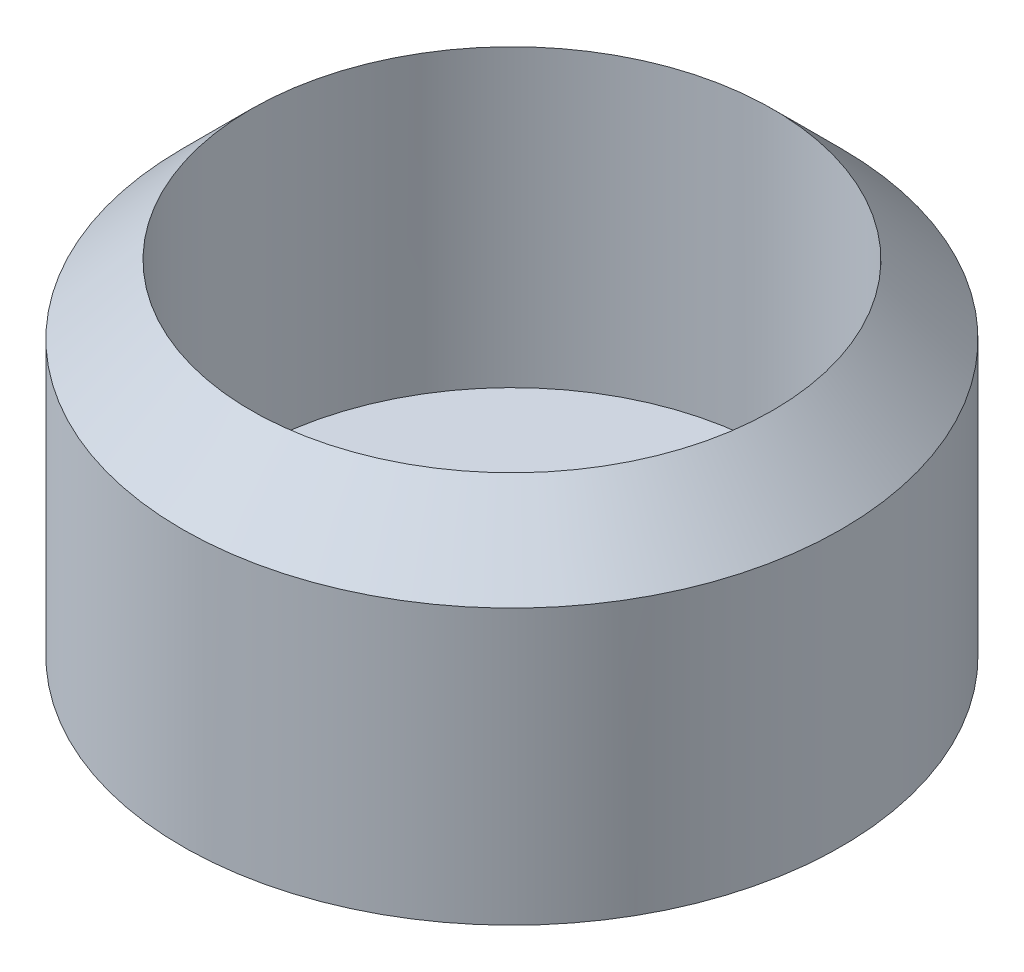
SolidWorks part; units mm, degrees
ref_plane "Front Plane" through (0, 0, 0) normal (0, 0, 1) x (1, 0, 0)
ref_plane "Top Plane" through (0, 0, 0) normal (0, 1, 0) x (1, 0, 0)
ref_plane "Right Plane" through (0, 0, 0) normal (1, 0, 0) x (0, 0, -1)
sketch "Sketch1" plane through (0, 0, 0) normal (0, 0, 1) x (1, 0, 0)
  line L6 (0, 0) -> (48, 0)
  line L7 (48, 0) -> (48, 50)
  line L8 (48, 50) -> (38, 50)
  line L9 (38, 50) -> (38, 7)
  line L10 (38, 7) -> (0, 7)
  line L11 (0, 7) -> (0, 0)
  dimension "D1" = 48
  dimension "D2" = 43
  dimension "D3" = 50
  dimension "D4" = 10
revolve "Revolve2" add sketch "Sketch1" angle 360 about L11
sketch "Sketch2" plane through (0, 0, 0) normal (0, -1, 0) x (1, 0, 0)
  circle A0 centre (0, 0) radius 22.5
  dimension "D1" = 45
extrude "Cut-Extrude1" cut sketch "Sketch2" against normal through all both and the other way through all
chamfer "Chamfer1" distance 10 angle 45 1 edges at (-48, 50, 0)
